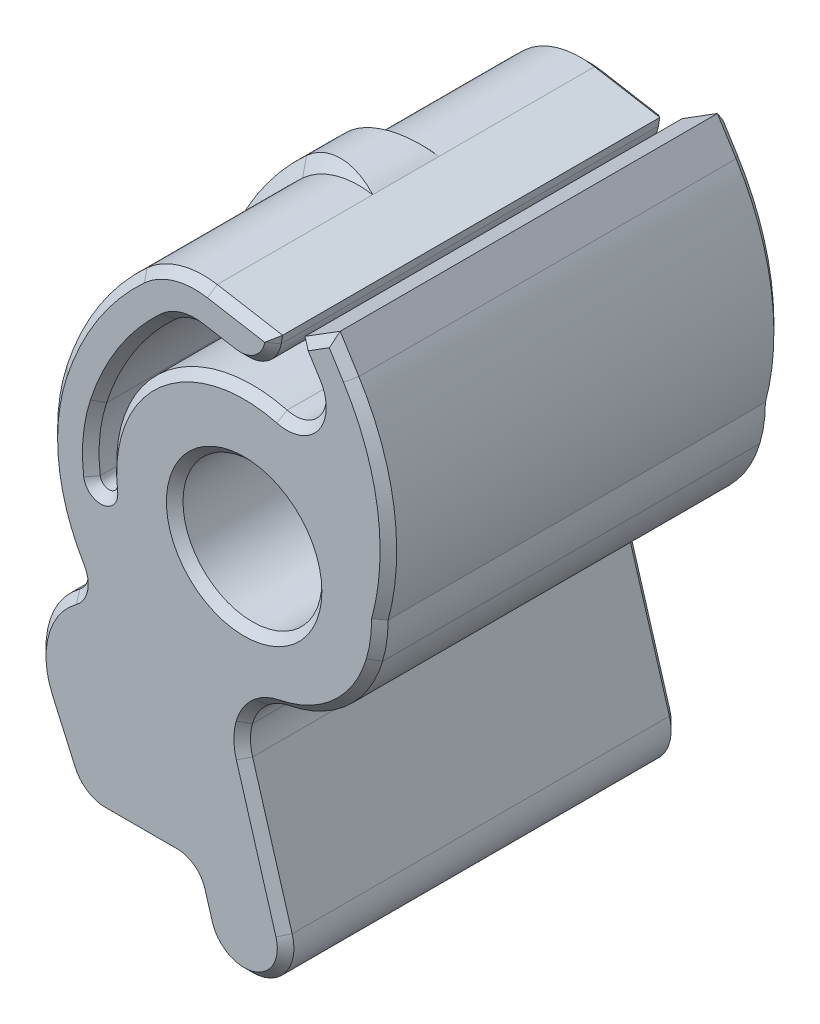
SolidWorks part; units mm, degrees
ref_plane "Front" through (0, 0, 0) normal (0, 0, 1) x (1, 0, 0)
ref_plane "Top" through (0, 0, 0) normal (0, 1, 0) x (1, 0, 0)
ref_plane "Right" through (0, 0, 0) normal (1, 0, 0) x (0, 0, -1)
sketch "Sketch1" plane through (0, 0, 0) normal (0, 0, 1) x (1, 0, 0)
  line L0 (-3.1398, -0.9313) -> (-0.9587, -8.2844)
  line L1 (0.9587, -8.2844) -> (3.1398, -0.9313)
  line L2 (0, 1.675) -> (0, 3.275) construction
  line L3 (0, -9) -> (0, 0) construction
  line L4 (0, 1.575) -> (0, 1.675) construction
  circle A0 centre (0, 0) radius 1.575 construction
  arc A1 (3.1398, -0.9313) -> (-3.1398, -0.9313) centre (0, 0) ccw
  arc A2 (-0.9587, -8.2844) -> (0.9587, -8.2844) centre (0, -8) ccw
  circle A5 centre (0, 0) radius 1.675
  dimension "D2" = 1
  dimension "D4" = 3.15
  dimension "D1" = 1.6
  dimension "D3" = 9
  dimension "D5" = 0.1
extrude "Boss-Extrude1" add sketch "Sketch1" along normal mid plane 10
sketch "Sketch2" plane through (0, 0, -5) normal (0, 0, -1) x (-1, 0, 0)
  line L2 (-3.1398, -0.9313) -> (-0.9587, -8.2844)
  line L3 (0.9587, -8.2844) -> (3.1398, -0.9313)
  line L4 (-3.1398, -0.9313) -> (-0.9587, -8.2844)
  line L5 (0.9587, -8.2844) -> (3.1398, -0.9313)
  arc A2 (3.1398, -0.9313) -> (-3.1398, -0.9313) centre (0, 0) ccw
  arc A3 (-0.9587, -8.2844) -> (0.9587, -8.2844) centre (0, -8) ccw
  arc A4 (3.1398, -0.9313) -> (-3.1398, -0.9313) centre (0, 0) ccw
  arc A5 (-0.9587, -8.2844) -> (0.9587, -8.2844) centre (0, -8) ccw
  dimension "D1" = 0
extrude "Movement Clearance" cut sketch "Sketch2" against normal blind 0.25
mirror "Movement Clearance 2" about plane through (0, 0, 0) normal (0, 0, 1) of "Movement Clearance"
sketch "Sketch6" plane through (0, 0, 0) normal (0, 0, 1) x (1, 0, 0)
  circle A7 centre (0, 0) radius 5.625 construction
  dimension "D3" = 11.25
sketch "Sketch19" plane through (0, 0, 0) normal (0, 0, 1) x (1, 0, 0)
  line L0 (-1.2431, -7.3257) -> (-3.3437, -7.3257)
  line L1 (-3.1398, -0.9313) -> (-0.9587, -8.2844) construction
  line L2 (-4.2572, -6.7324) -> (-4.8066, -5.4986)
  line L3 (-3.7929, -2.858) -> (-2.7112, -2.3764)
  line L4 (-2.7112, -2.3764) -> (-1.2431, -7.3257)
  line L5 (-0.9587, -8.2844) -> (-3.1398, -0.9313) construction
  arc A0 (-4.8066, -5.4986) -> (-3.7929, -2.858) centre (-2.9795, -4.6851) cw
  arc A1 (-3.3437, -7.3257) -> (-4.2572, -6.7324) centre (-3.3437, -6.3257) cw
  point P11 (-5.62, -3.6715)
  point P14 (-3.9931, -7.3257)
  dimension "D5" = 2
  dimension "D6" = 1
  dimension "D1" = 1
  dimension "D2" = 66
  dimension "D3" = 4
  dimension "D4" = 2.75
extrude "Closed Stopper" add sketch "Sketch19" along normal through all and the other way through all
fillet "Fillet12" radius 0.5 2 edges at (-1.2431, -7.3257, 0) (-2.7112, -2.3764, 0)
sketch "Sketch14" plane through (0, 0, 0) normal (0, 0, 1) x (1, 0, 0)
  line L0 (0, 0) -> (0.7276, 4.6754) construction
  line L3 (-0.8491, 4.9476) -> (0.7276, 4.6754)
  line L4 (-3.1119, -2.5548) -> (-3.7929, -2.858) construction
  line L5 (0, 0) -> (-4.47, 1.4524) construction
  line L6 (0, 0) -> (-2.54, 4.4517) construction
  line L7 (0, 0) -> (0, 3.275) construction
  line L8 (0, 0) -> (-1.5837, 4.4252) construction
  line L9 (-1.5837, 4.4252) -> (-1.7521, 4.8959) construction
  circle A0 centre (0, 0) radius 4.7 construction
  arc A2 (-3.7468, -2.8375) -> (-2.662, -3.8734) centre (0, 0) ccw
  arc A6 (-3.7468, -2.8375) -> (-4.47, 1.4524) centre (0, 0) cw
  arc A7 (-4.47, 1.4524) -> (-2.54, 4.4517) centre (2.1874, -0.7107) cw
  arc A8 (-2.54, 4.4517) -> (-0.8491, 4.9476) centre (-1.1893, 2.9767) cw
  dimension "D3" = 2
  dimension "D4" = 1.6
  dimension "D10" = 72
  dimension "D2" = 0.5
  dimension "D5" = 1.5
  dimension "D8" = 7
  dimension "D7" = 9.4
  dimension "D6" = 52.309
extrude "Spring" add sketch "Sketch14" along normal through all and the other way through all thin
sketch "Sketch26" plane through (0, 0, 0) normal (0, 0, 1) x (1, 0, 0)
  line L0 (-3.1398, -0.9313) -> (-0.9587, -8.2844) construction
  line L1 (-3.1398, -0.9313) -> (-2.6502, -2.582)
  arc A3 (-3.5189, 1.1434) -> (-2.8731, -2.3314) centre (0, 0) ccw construction
  arc A7 (-3.6716, -0.4576) -> (-2.6502, -2.582) centre (0, 0) ccw
  arc A8 (-3.6716, -0.4576) -> (-3.2499, -0.405) centre (-3.4607, -0.4313) ccw
  arc A9 (3.1398, -0.9313) -> (-3.1398, -0.9313) centre (0, 0) ccw construction
  arc A10 (-3.2499, -0.405) -> (-3.1398, -0.9313) centre (0, 0) ccw
  dimension "D1" = 0.5
extrude "Spring Fillet 1" add sketch "Sketch26" along normal through all and the other way through all
fillet "Spring Fillet 2" radius 0.5 1 edges at (-3.7468, -2.8375, 0)
fillet "Spring Fillet 3" radius 0.8 1 edges at (0.5575, 3.69, 0)
sketch "Sketch27" plane through (0, 0, 0) normal (0, 0, 1) x (1, 0, 0)
  line L3 (2.5678, 4.7325) -> (2.1173, 5.4534)
  line L5 (0, -9) -> (0, 0) construction
  line L6 (0, 1.0097) -> (0, 0) construction
  line L7 (0, 0) -> (2.1173, 5.4534) construction
  arc A0 (3.1398, -0.9313) -> (-3.1398, -0.9313) centre (0, 0) ccw construction
  arc A3 (3.275, 0) -> (2.5678, 4.7325) centre (-2.5205, 1.553) ccw
  dimension "D2" = 32
  dimension "D1" = 6
  dimension "D3" = 0.85
  dimension "D4" = 5.85
extrude "Open Stopper" add sketch "Sketch27" along normal through all and the other way through all thin thin type one direction reverse wall 1
fillet "Open Stopper Fillet" radius 0.75 1 edges at (2.4393, 2.1852, 0)
sketch "Sketch25" plane through (0, 0, 0) normal (0, 0, 1) x (1, 0, 0)
  line L6 (0.7786, 4.9711) -> (-0.7981, 5.2432)
  arc A0 (-2.7426, 4.673) -> (-0.8491, 4.9476) centre (-1.5941, 3.4187) cw
  arc A23 (-4.8266, 1.3055) -> (-3.1166, -3.518) centre (-0.4827, 0.1305) ccw
  arc A24 (-4.47, 1.4524) -> (-3.7468, -2.8375) centre (0, 0) ccw construction
  arc A25 (-0.8491, 4.9476) -> (-2.54, 4.4517) centre (-1.1893, 2.9767) ccw construction
  arc A26 (-2.54, 4.4517) -> (-4.47, 1.4524) centre (2.1874, -0.7107) ccw construction
  arc A27 (-0.8491, 4.9476) -> (-2.54, 4.4517) centre (-1.1893, 2.9767) ccw
  arc A29 (-0.7981, 5.2432) -> (-2.7426, 4.673) centre (-1.1893, 2.9767) ccw
  arc A30 (-2.7426, 4.673) -> (-4.7553, 1.5451) centre (2.1874, -0.7107) ccw
  arc A31 (-4.7553, 1.5451) -> (-3.986, -3.0186) centre (0, 0) ccw
  arc A32 (-3.986, -3.0186) -> (-2.832, -4.1207) centre (0, 0) ccw
  arc A33 (-4.47, 1.4524) -> (-3.1166, -3.518) centre (0, 0) ccw
  arc A35 (-2.7426, 4.673) -> (-4.7553, 1.5451) centre (2.1874, -0.7107) ccw
  arc A36 (-4.7553, 1.5451) -> (-4.8266, 1.3055) centre (0, 0) ccw
  arc A37 (-2.54, 4.4517) -> (-4.47, 1.4524) centre (2.1874, -0.7107) ccw
  dimension "D2" = 4.5
  dimension "D3" = 0.25
  dimension "D1" = 0.3
extrude "Friction Rib" add sketch "Sketch25" along normal mid plane 1
chamfer "Friction Rib Chamfer" distance 0.3 angle 45 8 edges at (-4.6702, -0.5286, -0.5) (-1.7521, 4.8959, -0.5) (-3.6992, 3.077, -0.5) (-4.6702, -0.5286, 0.5) (-1.7521, 4.8959, 0.5) (-3.6992, 3.077, 0.5) (-3.9733, -2.5624, -0.5) (-3.9733, -2.5624, 0.5)
sketch "Sketch8" plane through (0, 0, 0) normal (0, 0, 1) x (1, 0, 0)
  line L1 (3.1398, -0.9313) -> (0.9587, -8.2844) construction
  line L2 (3.1398, -0.9313) -> (0.9587, -8.2844)
  line L3 (0.3841, -3.2169) -> (-2.0029, -5.1648) construction
  line L4 (0.9587, -8.2844) -> (3.1398, -0.9313) construction
  line L5 (3.1398, -0.9313) -> (0.9587, -8.2844) construction
  line L6 (0.9587, -7.7156) -> (0.0038, -4.4965)
  line L7 (-3.1398, -0.9313) -> (-0.9587, -8.2844) construction
  line L8 (0, -9) -> (0, 0) construction
  arc A0 (0.9587, -8.2844) -> (0.9587, -7.7156) centre (0, -8) ccw
  arc A6 (0.0038, -4.4965) -> (0, -3.8009) centre (1.1987, -4.1421) cw
  arc A7 (0, -3.8009) -> (0.3841, -3.2169) centre (1.1211, -4.12) cw
  arc A8 (0.3841, -3.2169) -> (0.8896, -2.9793) centre (1.112, -4.1087) cw
  arc A9 (0.8896, -2.9793) -> (3.1398, -0.9313) centre (0.3221, -0.0955) ccw
  arc A10 (-0.9587, -8.2844) -> (0.9587, -8.2844) centre (0, -8) ccw construction
extrude "Clearance Cut" cut sketch "Sketch8" against normal through all both and the other way through all
chamfer "Deburs" distance 0.2 angle 45 64 edges at (-3.6833, 0.3513, 4.75) (-3.6833, 0.3513, -4.75) (-2.1545, 2.4665, 4.75) (-2.1545, 2.4665, -4.75) (-3.4344, -0.6422, 4.75) (-3.4344, -0.6422, -4.75) (-4.9129, -4.1734, -4.75) (-4.9129, -4.1734, 4.75) (-4.6702, -0.5286, 4.75) (-4.6702, -0.5286, -4.75) (-3.9711, -2.7701, -4.75) (-3.9711, -2.7701, 4.75) (0.3664, 3.9608, -4.75) (0.3664, 3.9608, 4.75) (3.241, -0.4705, 4.75) (3.241, -0.4705, -4.75) (2.3425, 5.093, -4.75) (1.6933, 5.1884, 4.75) (3.4136, 2.4398, -4.75) (3.4136, 2.4398, 4.75) (2.3425, 5.093, 4.75) (1.6933, 5.1884, -4.75) (1.4677, 4.6059, -4.75) (1.4677, 4.6059, 4.75) (1.6336, 3.4457, -4.75) (1.6336, 3.4457, 4.75) (-1.0478, -7.9839, -4.75) (0.2844, -8.9587, -4.75) (-1.675, 0, -4.75) (0.4813, -6.1061, -4.75) (-0.0476, -4.149, -4.75) (0.1473, -3.4794, -4.75) (0.6223, -3.067, -4.75) (2.3003, -2.2691, -4.75) (2.3003, -2.2691, 4.75) (0.6223, -3.067, 4.75) (0.1473, -3.4794, 4.75) (-0.0476, -4.149, 4.75) (0.4813, -6.1061, 4.75) (1.675, 0, 4.75) (0.2844, -8.9587, 4.75) (-1.0478, -7.9839, 4.75) (-4.5319, -6.1155, -4.75) (-3.8883, -7.1643, -4.75) (-2.48, -7.3257, -4.75) (-4.5319, -6.1155, 4.75) (-3.8883, -7.1643, 4.75) (-2.48, -7.3257, 4.75) (-1.3172, -7.425, -4.75) (-1.3172, -7.425, 4.75) (-2.8583, 2.5359, 4.75) (-1.4707, 3.9363, 4.75) (-0.6251, 3.8941, 4.75) (-3.6992, 3.077, -4.75) (-1.7521, 4.8959, -4.75) (-0.0608, 4.8115, -4.75) (0.7106, 4.5769, -4.75) (-0.6251, 3.8941, -4.75) (0.7106, 4.5769, 4.75) (-0.0608, 4.8115, 4.75) (-1.7521, 4.8959, 4.75) (-3.6992, 3.077, 4.75) (-2.8583, 2.5359, -4.75) (-1.4707, 3.9363, -4.75)
equation "\"D4@Sketch1\"=\"Hardware Clearance Hole Diameter@Box Assy.SLDASM\""
equation "\"D1@Boss-Extrude1\"=\"Hardware Length@Box Assy.Assembly\"/2"
